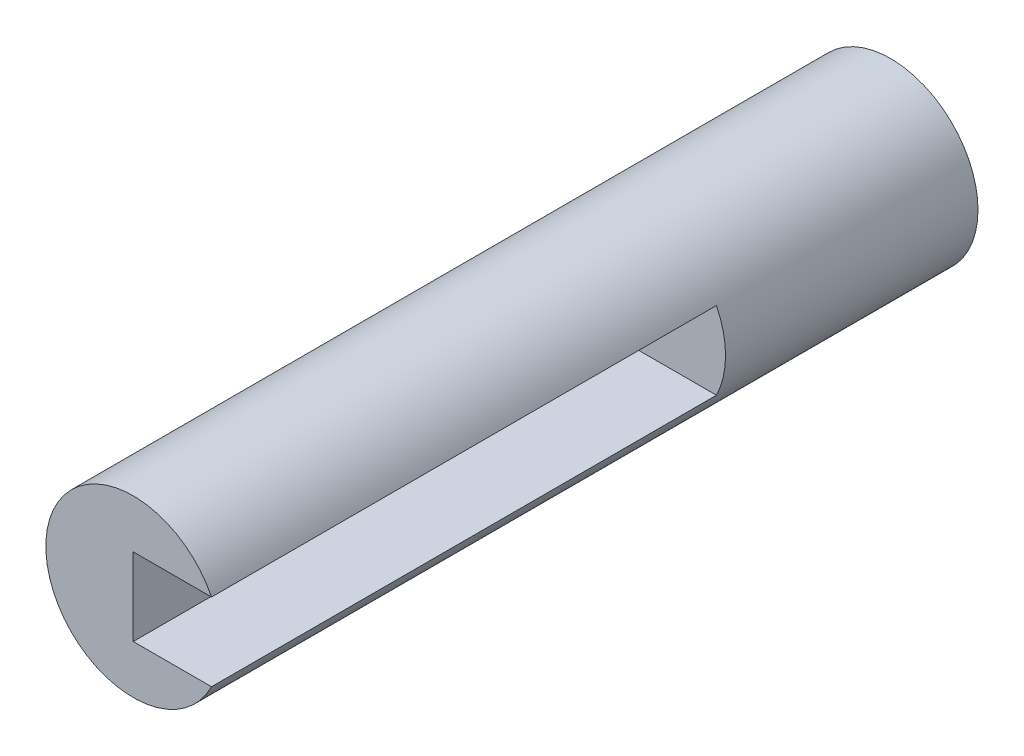
SolidWorks part; units mm, degrees
ref_plane "Front Plane" through (0, 0, 0) normal (0, 0, 1) x (1, 0, 0)
ref_plane "Top Plane" through (0, 0, 0) normal (0, 1, 0) x (1, 0, 0)
ref_plane "Right Plane" through (0, 0, 0) normal (1, 0, 0) x (0, 0, -1)
sketch "Sketch1" plane through (0, 0, 0) normal (0, 0, 1) x (1, 0, 0)
  circle A0 centre (-11.3049, 8.134) radius 4.5
extrude "Boss-Extrude3" add sketch "Sketch1" along normal blind 39
sketch "Sketch3" plane through (0, 0, 0) normal (0, 0, 1) x (1, 0, 0)
  line L1 (-9.0683, 9.734) -> (-13.5415, 9.734)
  line L3 (-9.0683, 6.534) -> (-13.5415, 6.534)
  circle A0 centre (-11.3049, 8.134) radius 2.75
  circle A1 centre (-11.3049, 8.134) radius 4.5 construction
  dimension "D2" = 5.5
  dimension "D1" = 0
  dimension "D3" = 1.6
  dimension "D4" = 1.6
extrude "Cut-Extrude2" cut sketch "Sketch3" along normal blind 2.5 contours L1 A0 | L3 A0 region at (-11.3049, 10.2034, 0) region at (-11.3049, 6.0646, 0)
extrude "Cut-Extrude3" cut sketch "Sketch3<4>" along normal blind 8.5 contours L1 A0 L3 region at (-11.3049, 8.134, 0)
sketch "Sketch3<4>" plane through (0, 0, 0) normal (0, 0, 1) x (1, 0, 0) same geometry as "Sketch3"
ref_plane "Plane7" through (0, 0, 39) normal (0, 0, 1) x (1, 0, 0)
sketch "Sketch6" plane through (0, 0, 39) normal (0, 0, 1) x (1, 0, 0)
  line L1 (-11.3049, 10.134) -> (-3.3593, 10.134)
  line L2 (-11.3049, 10.134) -> (-11.3049, 6.134)
  line L3 (-11.3049, 6.134) -> (-3.3593, 6.134)
  line L4 (-3.3593, 10.134) -> (-3.3593, 6.134)
  circle A0 centre (-11.3049, 8.134) radius 4.5 construction
  dimension "D1" = 0
  dimension "D2" = 2
  dimension "D3" = 2
extrude "Cut-Extrude4" cut sketch "Sketch6" against normal blind 26
fillet "Fillet1" radius 0.5 2 edges at (-11.3049, 6.534, 2.5) (-11.3049, 9.734, 2.5)
